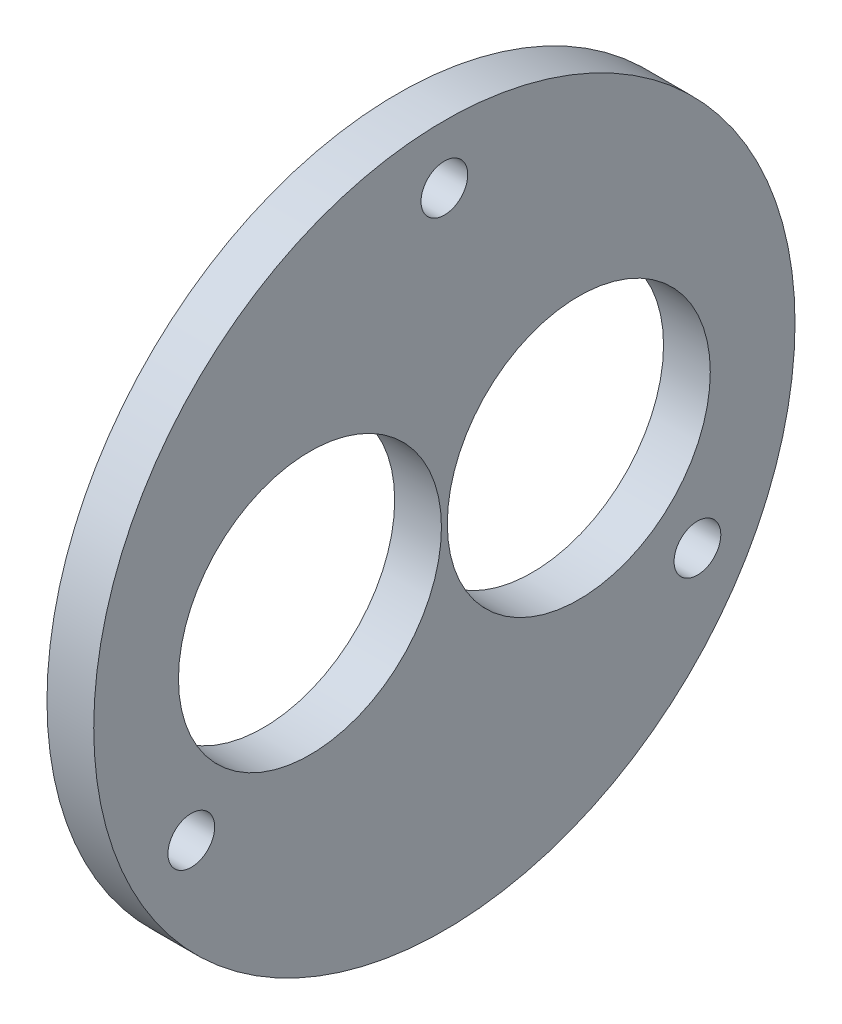
SolidWorks part; units mm, degrees
ref_plane "Front Plane" through (0, 0, 0) normal (0, 0, 1) x (1, 0, 0)
ref_plane "Top Plane" through (0, 0, 0) normal (0, 1, 0) x (1, 0, 0)
ref_plane "Right Plane" through (0, 0, 0) normal (1, 0, 0) x (0, 0, -1)
sketch "Sketch1" plane through (0, 0, 0) normal (1, 0, 0) x (0, 0, -1)
  line L0 (0, 71.6561) -> (0, -95.6447) construction
  line L1 (-75.2705, 0) -> (80.9544, 0) construction
  circle A0 centre (0, 0) radius 60
  circle A1 centre (0, 50) radius 4
  circle A2 centre (43.3013, -25) radius 4
  circle A3 centre (-43.3013, -25) radius 4
  circle A4 centre (-23, 0) radius 22.5
  circle A5 centre (23, 0) radius 22.5
  point P14 (0, 0)
  dimension "D1" = 120
  dimension "D2" = 8
  dimension "D5" = 45
  dimension "D3" = 50
  dimension "D6" = 23
  dimension "D4" = 3
extrude "Boss-Extrude1" add sketch "Sketch1" along normal blind 8
